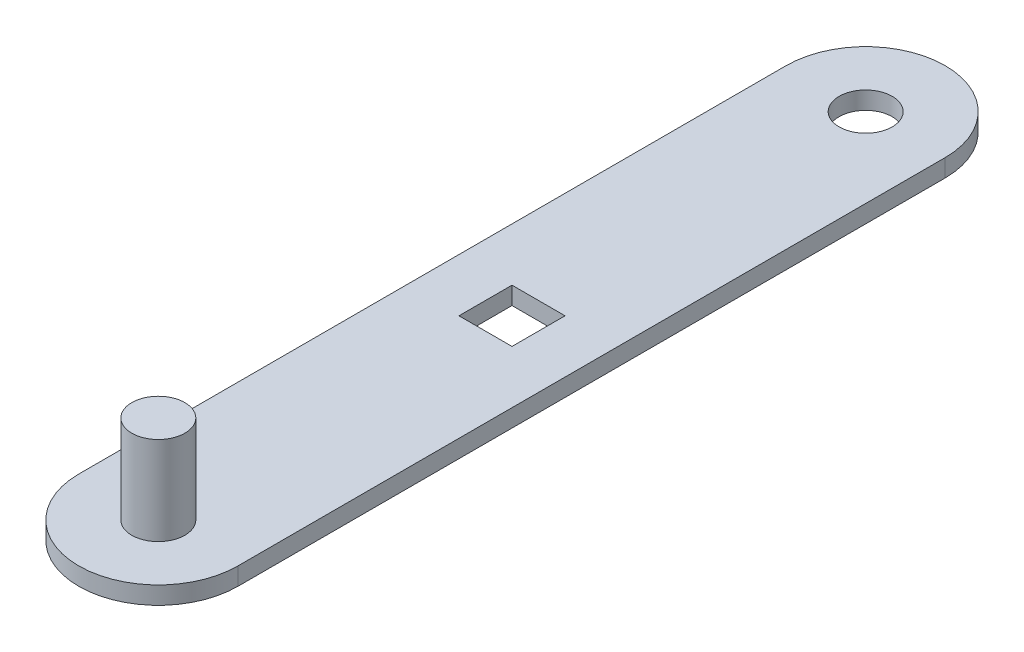
SolidWorks part; units mm, degrees
ref_plane "Front Plane" through (0, 0, 0) normal (0, 0, 1) x (1, 0, 0)
ref_plane "Top Plane" through (0, 0, 0) normal (0, 1, 0) x (1, 0, 0)
ref_plane "Right Plane" through (0, 0, 0) normal (1, 0, 0) x (0, 0, -1)
sketch "Sketch1" plane through (0, 0, 0) normal (0, 1, 0) x (1, 0, 0)
  line L1 (-225, -1000) -> (225, -1000)
  line L2 (-225, -1000) -> (-225, 1000)
  line L3 (-225, 1000) -> (225, 1000)
  line L4 (225, -1000) -> (225, 1000)
  line L5 (-225, -1000) -> (225, 1000) construction
  line L6 (-225, 1000) -> (225, -1000) construction
  arc A0 (225, -1000) -> (-225, -1000) centre (0, -1000) cw
  arc A1 (225, 1000) -> (-225, 1000) centre (0, 1000) ccw
  point P0 (0, 0)
  dimension "D1" = 2000
  dimension "D2" = 450
extrude "Boss-Extrude1" add sketch "Sketch1" along normal blind 50 contours L1 L4 L3 L2 | L3 A1 | A0 L1 region at (0, 0, 0) region at (0, 0, 1095.493) region at (0, 0, -1095.493)
sketch "Sketch2" plane through (0, 50, 0) normal (0, 1, 0) x (1, 0, 0)
  line L0 (-225, -1000) -> (225, -1000)
  line L1 (-225, -1000) -> (-225, 1000) construction
  circle A0 centre (0, -1000) radius 75
extrude "Boss-Extrude2" add sketch "Sketch2" along normal blind 250 contours L0 A0 | L0 A0 region at (0, 50, 968.169) region at (0, 50, 1031.831)
sketch "Sketch3" plane through (0, 50, 0) normal (0, 1, 0) x (1, 0, 0)
  line L0 (-225, 1000) -> (225, 1000)
  circle A0 centre (0, 1000) radius 75
extrude "Cut-Extrude2" cut sketch "Sketch3" against normal blind 250 contours L0 A0 | L0 A0 region at (0, 50, -1031.831) region at (0, 50, -968.169)
sketch "Sketch4" plane through (0, 50, 0) normal (0, 1, 0) x (1, 0, 0)
  line L1 (-75, -75) -> (75, -75)
  line L2 (-75, -75) -> (-75, 75)
  line L3 (-75, 75) -> (75, 75)
  line L4 (75, -75) -> (75, 75)
  line L5 (-75, -75) -> (75, 75) construction
  line L6 (-75, 75) -> (75, -75) construction
  point P0 (0, 0)
  dimension "D1" = 150
  dimension "D2" = 150
extrude "Cut-Extrude3" cut sketch "Sketch4" against normal through all
